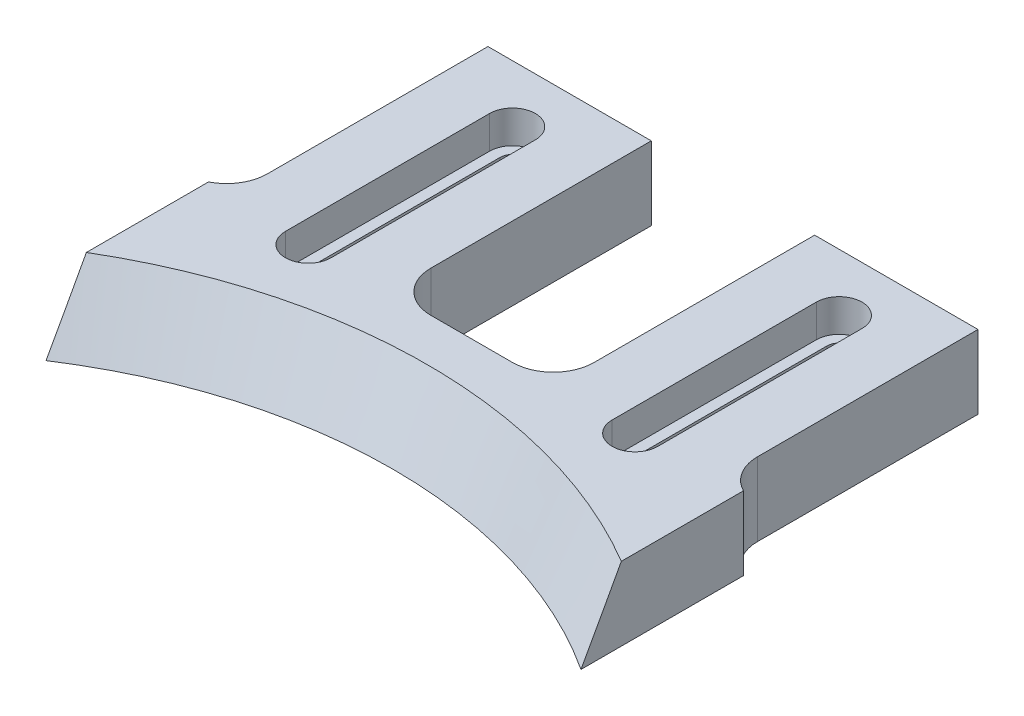
SolidWorks part; units mm, degrees
material "POM Acetal Copolymer"
ref_plane "Front Plane" through (0, 0, 0) normal (0, 0, 1) x (1, 0, 0)
ref_plane "Top Plane" through (0, 0, 0) normal (0, 1, 0) x (1, 0, 0)
ref_plane "Right Plane" through (0, 0, 0) normal (1, 0, 0) x (0, 0, -1)
sketch "Sketch1" plane through (0, 0, 0) normal (0, 1, 0) x (1, 0, 0)
  line L0 (0, 0) -> (0, 55)
  line L1 (0, 55) -> (75.5, 55)
  line L2 (75.5, 55) -> (75.5, 0)
  arc A0 (0, 0) -> (75.5, 0) centre (37.75, -46.6362) cw
  dimension "D5" = 60
  dimension "D1" = 55
  dimension "D3" = 75.5
extrude "Boss-Extrude1" add sketch "Sketch1" along normal blind 9
sketch "Sketch4" plane through (0, 9, 0) normal (0, 1, 0) x (1, 0, 0)
  line L0 (17.75, 48) -> (17.75, 23) construction
  line L1 (19.25, 48) -> (19.25, 23)
  line L2 (16.25, 48) -> (16.25, 23)
  line L3 (57.75, 48) -> (57.75, 23) construction
  line L4 (59.25, 48) -> (59.25, 23)
  line L5 (56.25, 48) -> (56.25, 23)
  line L6 (75.5, 55) -> (0, 55) construction
  line L9 (75.5, 55) -> (0, 55) construction
  arc A0 (19.25, 48) -> (16.25, 48) centre (17.75, 48) ccw
  arc A1 (16.25, 23) -> (19.25, 23) centre (17.75, 23) ccw
  arc A2 (59.25, 48) -> (56.25, 48) centre (57.75, 48) ccw
  arc A3 (56.25, 23) -> (59.25, 23) centre (57.75, 23) ccw
  point P2 (17.75, 35.5)
  point P7 (57.75, 35.5)
  point P14 (37.75, 55)
  dimension "D1" = 3
  dimension "D2" = 3
  dimension "D3" = 40
  dimension "D4" = 20
  dimension "D5" = 25
  dimension "D6" = 7
extrude "Cut-Extrude2" cut sketch "Sketch4" against normal up to next
sketch "Sketch5" plane through (0, 9, 0) normal (0, 1, 0) x (1, 0, 0)
  line L0 (75.5, 55) -> (0, 55) construction
  line L1 (27.75, 55) -> (47.75, 55)
  line L2 (27.75, 55) -> (27.75, 23)
  line L3 (27.75, 23) -> (47.75, 23)
  line L4 (47.75, 55) -> (47.75, 23)
  line L7 (67.75, 55) -> (75.5, 55)
  line L8 (0, 55) -> (7.75, 55)
  line L9 (0, 55) -> (0, 23)
  line L10 (0, 23) -> (7.75, 23)
  line L11 (7.75, 55) -> (7.75, 23)
  line L12 (67.75, 55) -> (67.75, 23)
  line L13 (67.75, 23) -> (75.5, 23)
  line L14 (75.5, 55) -> (75.5, 23)
  arc A0 (19.25, 48) -> (16.25, 48) centre (17.75, 48) ccw construction
  arc A1 (59.25, 48) -> (56.25, 48) centre (57.75, 48) ccw construction
  point P6 (17.75, 49.5)
  point P21 (57.75, 49.5)
  dimension "D1" = 20
  dimension "D2" = 20
  dimension "D3" = 32
  dimension "D4" = 10
  dimension "D5" = 10
extrude "Cut-Extrude3" cut sketch "Sketch5" against normal blind 10
fillet "Fillet1" radius 5 4 edges at (67.75, 4.5, -23) (47.75, 4.5, -23) (27.75, 4.5, -23) (7.75, 4.5, -23)
sketch "Sketch6" plane through (0, 9, 0) normal (0, 1, 0) x (1, 0, 0)
  line L0 (17.75, 48) -> (17.75, 23) construction
  line L1 (20.55, 48) -> (20.55, 23)
  line L2 (14.95, 48) -> (14.95, 23)
  line L3 (57.75, 48) -> (57.75, 23) construction
  line L4 (60.55, 48) -> (60.55, 23)
  line L5 (54.95, 48) -> (54.95, 23)
  arc A0 (20.55, 48) -> (14.95, 48) centre (17.75, 48) ccw
  arc A1 (14.95, 23) -> (20.55, 23) centre (17.75, 23) ccw
  arc A2 (60.55, 48) -> (54.95, 48) centre (57.75, 48) ccw
  arc A3 (54.95, 23) -> (60.55, 23) centre (57.75, 23) ccw
  point P4 (17.75, 35.5)
  point P9 (57.75, 35.5)
  dimension "D1" = 5.6
  dimension "D2" = 5.6
extrude "Cut-Extrude4" cut sketch "Sketch6" against normal blind 4
chamfer "Chamfer1" distance 9 angle 25 1 edges at (37.75, 9, -13.3638) first distance on face at (37.75, 4.5, -6.6819)
sketch "Sketch7" plane through (0, 9, 0) normal (0, 1, 0) x (1, 0, 0)
  line L1 (0, 0) -> (5, 0)
  line L2 (0, 0) -> (0, 33.0851)
  line L3 (0, 33.0851) -> (5, 33.0851)
  line L4 (5, 0) -> (5, 33.0851)
  line L5 (75.5, 0) -> (70.5, 0)
  line L6 (75.5, 0) -> (75.5, 33.7453)
  line L7 (75.5, 33.7453) -> (70.5, 33.7453)
  line L8 (70.5, 0) -> (70.5, 33.7453)
  dimension "D1" = 5
extrude "Cut-Extrude5" cut sketch "Sketch7" against normal up to next
